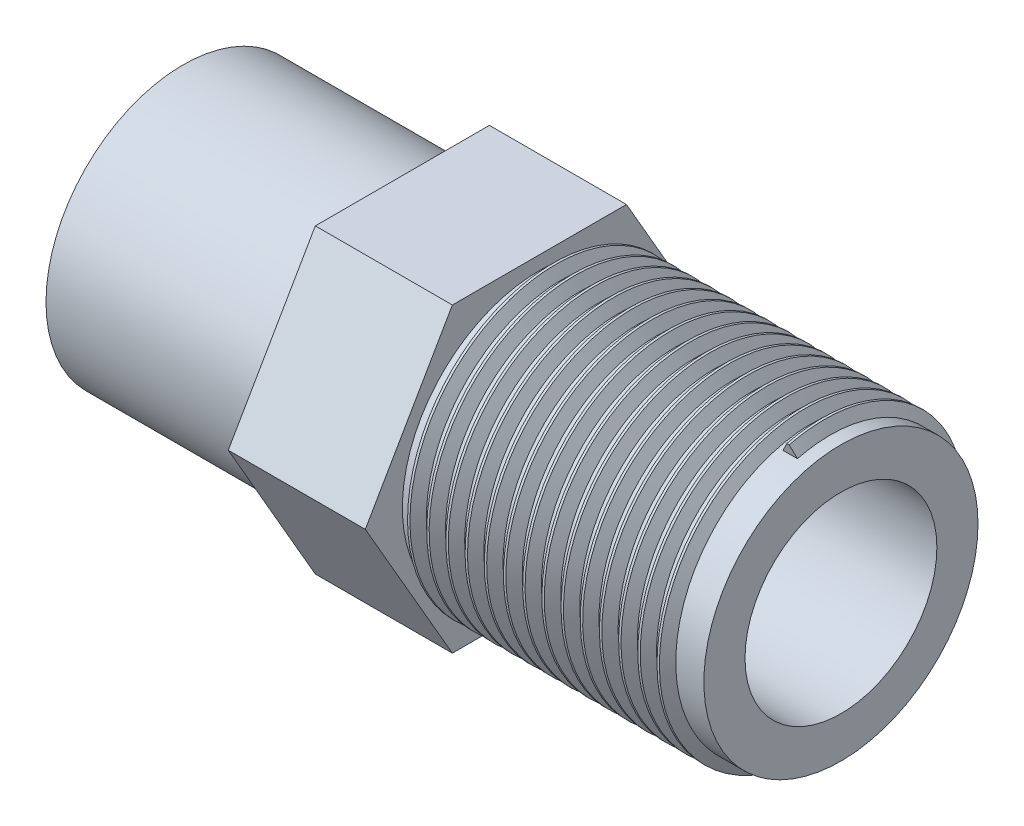
SolidWorks part; units mm, degrees
ref_plane "Front Plane" through (0, 0, 0) normal (0, 0, 1) x (1, 0, 0)
ref_plane "Top Plane" through (0, 0, 0) normal (0, 1, 0) x (1, 0, 0)
ref_plane "Right Plane" through (0, 0, 0) normal (1, 0, 0) x (0, 0, -1)
sketch "Sketch1" plane through (0, 0, 0) normal (1, 0, 0) x (0, 0, -1)
  circle A0 centre (0, 0) radius 5
  circle A1 centre (0, 0) radius 3.5
  dimension "D1" = 7
  dimension "D2" = 10
extrude "Boss-Extrude1" add sketch "Sketch1" along normal mid plane 11
sketch "Sketch2" plane through (-5.5, 0, 0) normal (-1, 0, 0) x (0, 0, 1)
  line L1 (6.3509, 0) -> (3.1754, 5.5)
  line L2 (3.1754, 5.5) -> (-3.1754, 5.5)
  line L3 (-3.1754, 5.5) -> (-6.3509, 0)
  line L4 (-6.3509, 0) -> (-3.1754, -5.5)
  line L5 (-3.1754, -5.5) -> (3.1754, -5.5)
  line L6 (3.1754, -5.5) -> (6.3509, 0)
  circle A0 centre (0, 0) radius 5.5 construction
  circle A1 centre (0, 0) radius 5 construction
  dimension "D1" = 11
extrude "Boss-Extrude2" add sketch "Sketch2" along normal blind 5
sketch "Sketch3" plane through (-10.5, 0, 0) normal (-1, 0, 0) x (0, 0, 1)
  circle A0 centre (0, 0) radius 5
  dimension "D1" = 10
extrude "Boss-Extrude3" add sketch "Sketch3" along normal blind 8
sketch "Sketch4" plane through (-18.5, 0, 0) normal (-1, 0, 0) x (0, 0, 1)
  circle A0 centre (0, 0) radius 3.5
  circle A1 centre (0, 0) radius 5 construction
  dimension "D1" = 7
extrude "Cut-Extrude1" cut sketch "Sketch4" against normal up to next
thread "Thread1" pitch 0.7 method extrude profile "Thread Profile1" start angle 0, offset 0, length 10, pitch 0.7, diameter 10
ref_plane "Plane1" through (-5.5, 0, -5) normal (0, -1, 0) x (0, 0, -1)
sketch "Thread Profile1" plane through (-5.5, 0, -5) normal (0, -1, 0) x (0, 0, -1)
  line L0 (0, 0) -> (0, 0.7) construction
  line L1 (0, 0) -> (0.3789, 0.2187)
  line L2 (0.3789, 0.2187) -> (0.3789, 0.3062)
  line L3 (0.3789, 0.3062) -> (0, 0.525)
  line L4 (0.3789, 0.2625) -> (0, 0.2625) construction
  line L11 (0, 0) -> (0, 0.525)
  point P2 (0, 0)
  dimension "Pitch" = 0.7
  dimension "Profile_Angle" = 60
  dimension "Profile_Land" = 0.0875
  dimension "Profile_Height" = 0.3789
